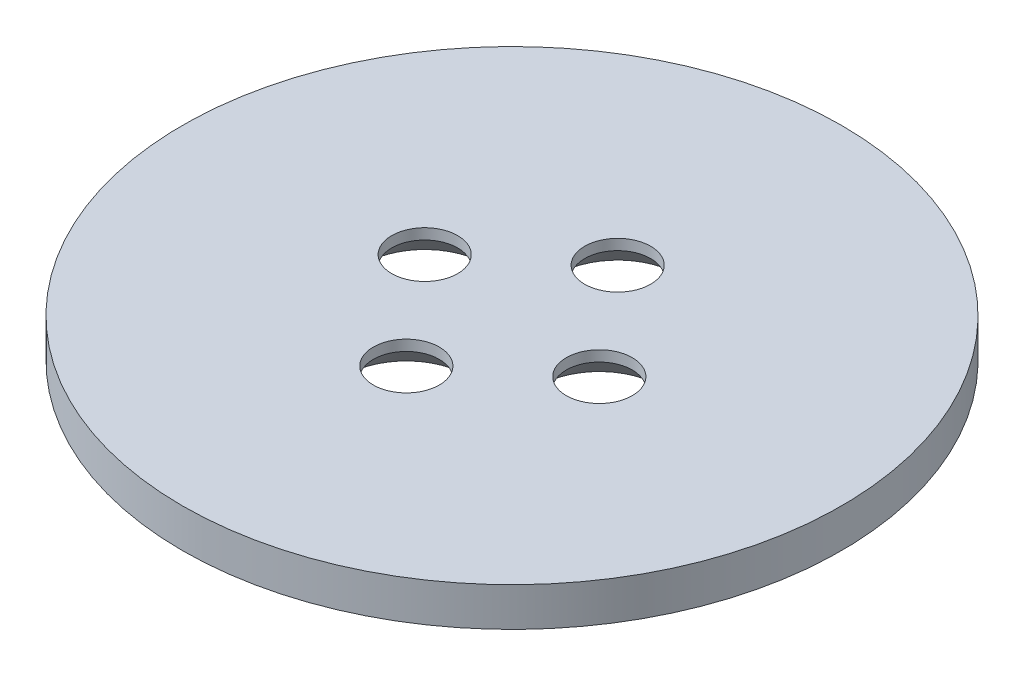
SolidWorks part; units mm, degrees
ref_plane "Front Plane" through (0, 0, 0) normal (0, 0, 1) x (1, 0, 0)
ref_plane "Top Plane" through (0, 0, 0) normal (0, 1, 0) x (1, 0, 0)
ref_plane "Right Plane" through (0, 0, 0) normal (1, 0, 0) x (0, 0, -1)
sketch "Sketch1" plane through (0, 0, 0) normal (0, 1, 0) x (1, 0, 0)
  circle A0 centre (0, 0) radius 17
  dimension "D1" = 34
extrude "Boss-Extrude1" add sketch "Sketch1" along normal blind 2
hole_wizard "CSK for M3 Countersunk Flat Head Screw1" positions "Sketch2" profile "Sketch3" countersink size "M3" standard "ISO" end condition up to next
sketch "Sketch2" plane through (0, 0, 0) normal (0, -1, 0) x (-1, 0, 0)
  point P0 (4.9774, 0.4744)
  point P2 (-0.4744, 4.9774)
  point P4 (-4.9774, -0.4744)
  point P6 (0.4744, -4.9774)
sketch "Sketch3" plane through (-4.9774, 0, -0.4744) normal (1, 0, 0) x (0, 0, -1)
  line L0 (0, 0) -> (0, 2)
  line L1 (0, 2) -> (1.7, 2)
  line L2 (1.7, 2) -> (1.7, 1.45)
  line L3 (1.7, 1.45) -> (3.15, 0)
  line L5 (3.15, 0) -> (0, 0)
  line L6 (-1.7, 1.45) -> (-3.15, 0) construction
  line L11 (0, -6.35) -> (0, 107.95) construction
  dimension "Thru Hole Dia." = 3.4
  dimension "Thru Hole Depth" = 2
  dimension "Near C'Sink Dia." = 6.3
  dimension "Near C'Sink Angle" = 90
